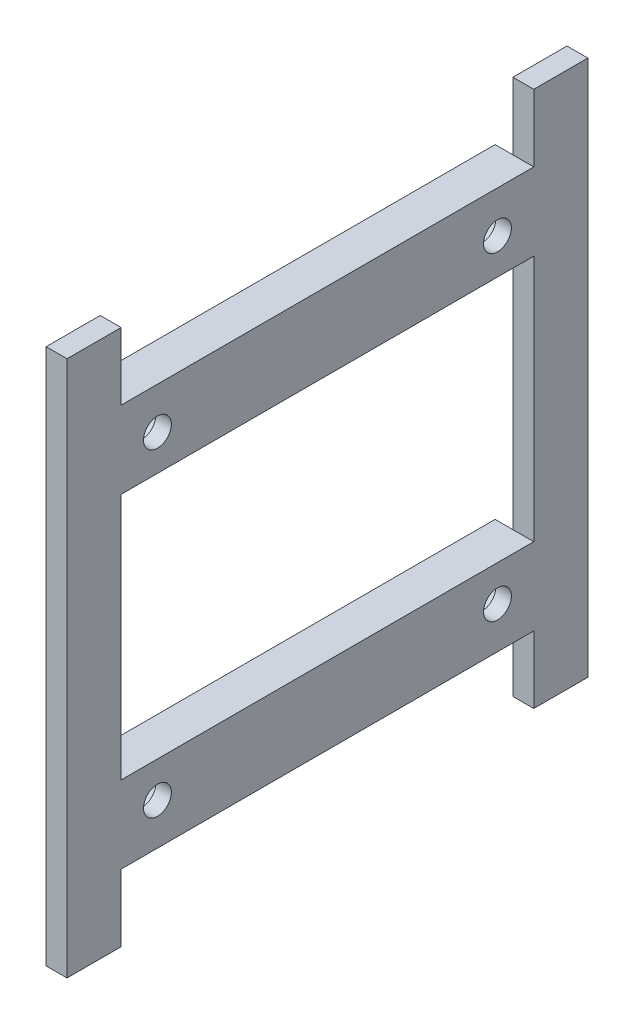
SolidWorks part; units mm, degrees
ref_plane "Front Plane" through (0, 0, 0) normal (0, 0, 1) x (1, 0, 0)
ref_plane "Top Plane" through (0, 0, 0) normal (0, 1, 0) x (1, 0, 0)
ref_plane "Right Plane" through (0, 0, 0) normal (1, 0, 0) x (0, 0, -1)
sketch "Sketch1" plane through (0, 0, 0) normal (1, 0, 0) x (0, 0, -1)
  line L0 (0, 0) -> (-13.3323, 0) construction
  line L1 (-33.7, 0) -> (-26.7, 0)
  line L2 (-33.7, -34.7) -> (-33.7, 34.7)
  line L3 (-33.7, 34.7) -> (-26.7, 34.7)
  line L4 (-26.7, -34.7) -> (-26.7, 34.7)
  line L5 (-26.7, 26) -> (26.7, 26)
  line L6 (-26.7, 26) -> (-26.7, 16)
  line L7 (-26.7, 16) -> (26.7, 16)
  line L8 (0, 26) -> (0, 16)
  line L13 (0, 0) -> (0, 7.6232) construction
  line L14 (33.7, 34.7) -> (26.7, 34.7)
  line L15 (26.7, -34.7) -> (26.7, 34.7)
  line L16 (33.7, 0) -> (26.7, 0)
  line L17 (33.7, -34.7) -> (33.7, 34.7)
  line L18 (26.7, 26) -> (26.7, 16)
  line L19 (33.7, -34.7) -> (26.7, -34.7)
  line L20 (-33.7, -34.7) -> (-26.7, -34.7)
  line L21 (-26.7, -26) -> (-26.7, -16)
  line L22 (-26.7, -26) -> (26.7, -26)
  line L23 (26.7, -26) -> (26.7, -16)
  line L24 (-26.7, -16) -> (26.7, -16)
  circle A0 centre (-22, 20.6259) radius 1.8
  circle A1 centre (22, 20.6259) radius 1.8
  circle A2 centre (22, -20.6259) radius 1.8
  circle A3 centre (-22, -20.6259) radius 1.8
  dimension "D5" = 22
  dimension "D7" = 3.6
  dimension "D1" = 34.7
  dimension "D2" = 16
  dimension "D3" = 7
  dimension "D4" = 10
  dimension "D6" = 26.7
extrude "Boss-Extrude1" add sketch "Sketch1" against normal blind 2.7 contours L2 L3 L4 L20 | L17 L14 L15 L19
extrude "Boss-Extrude2" add sketch "Sketch1<7>" against normal blind 5 contours A0 | A1 | L5 L18 L7 L6 | L24 L23 L22 L21 | A3 | A2
sketch "Sketch1<7>" plane through (0, 0, 0) normal (1, 0, 0) x (0, 0, -1) same geometry as "Sketch1"
sketch "Sketch2" plane through (-5, 0, 0) normal (-1, 0, 0) x (0, 0, 1)
  circle A0 centre (-22, 20.6259) radius 3.15
  circle A1 centre (22, 20.6259) radius 3.15
  circle A2 centre (-22, -20.6259) radius 3.15
  circle A3 centre (22, -20.6259) radius 3.15
extrude "Cut-Extrude1" cut sketch "Sketch2" against normal blind 3
